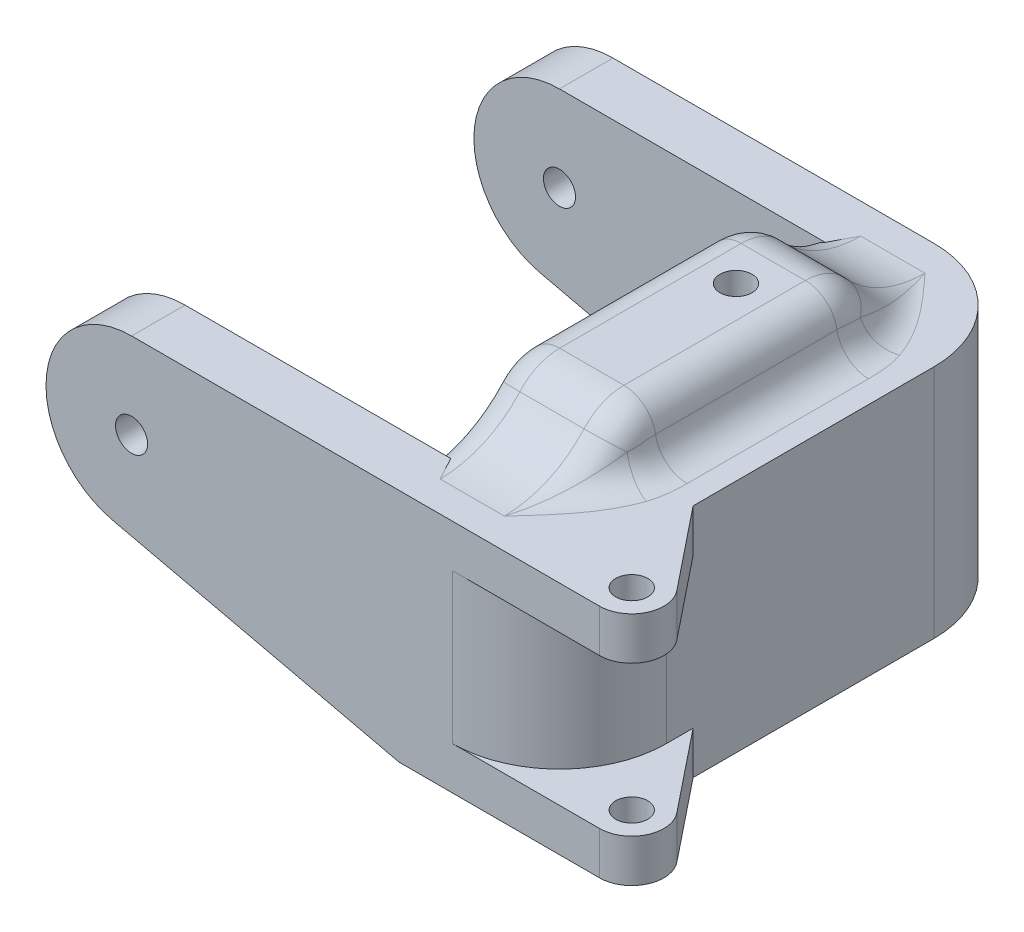
SolidWorks part; units mm, degrees
ref_plane "前视基准面" through (0, 0, 0) normal (0, 0, 1) x (1, 0, 0)
ref_plane "上视基准面" through (0, 0, 0) normal (0, 1, 0) x (1, 0, 0)
ref_plane "右视基准面" through (0, 0, 0) normal (1, 0, 0) x (0, 0, -1)
sketch "草图1" plane through (0, 0, 0) normal (0, 0, 1) x (1, 0, 0)
  line L0 (0.5609, -11) -> (27.3655, -4.7938)
  line L1 (0.5609, -11) -> (-14.4391, -11)
  line L3 (0.5609, 11) -> (-14.4391, 11)
  line L4 (-14.4391, -11) -> (-14.4391, 11)
  line L7 (0.5609, 11) -> (25.5609, 11)
  arc A1 (27.3655, -4.7938) -> (25.5609, 11) centre (25.5609, 3) ccw
  circle A2 centre (25.5609, 3) radius 1.5
  point P0 (0, 0)
  dimension "D4" = 8
  dimension "D5" = 3
  dimension "D1" = 22
  dimension "D2" = 15
  dimension "D3" = 25
extrude "凸台-拉伸1" add sketch "草图1" along normal blind 45
sketch "草图2" plane through (0, 11, 0) normal (0, 1, 0) x (1, 0, 0)
  line L0 (25.5609, 0) -> (-14.4391, 0) construction
  line L1 (-9.4391, -5) -> (42.9728, -5)
  line L2 (-9.4391, -5) -> (-9.4391, -40)
  line L3 (-9.4391, -40) -> (42.9728, -40)
  line L4 (42.9728, -5) -> (42.9728, -40)
  line L7 (-14.4391, -45) -> (-14.4391, 0) construction
  dimension "D1" = 35
  dimension "D2" = 52.4118
  dimension "D3" = 5
  dimension "D4" = 5
extrude "切除-拉伸1" cut sketch "草图2" against normal through all
sketch "草图4" plane through (0, -11, 0) normal (0, -1, 0) x (1, 0, 0)
  line L1 (-9.4391, 40) -> (2.5609, 40)
  line L2 (-9.4391, 40) -> (-9.4391, 33.5)
  line L3 (-9.4391, 33.5) -> (2.5609, 33.5)
  line L4 (2.5609, 40) -> (2.5609, 33.5)
  line L5 (-9.4391, 5) -> (2.5609, 5)
  line L6 (-9.4391, 5) -> (-9.4391, 11.5)
  line L7 (-9.4391, 11.5) -> (2.5609, 11.5)
  line L8 (2.5609, 5) -> (2.5609, 11.5)
  dimension "D1" = 6.5
  dimension "D2" = 12
  dimension "D3" = 6.5
  dimension "D4" = 12
extrude "凸台-拉伸2" add sketch "草图4" against normal blind 12
sketch "草图6" plane through (2.5609, 0, 0) normal (1, 0, 0) x (0, 0, -1)
  line L1 (-33.5, -11) -> (-40, -11)
  line L2 (-33.5, -11) -> (-33.5, -8.5)
  line L3 (-33.5, -8.5) -> (-40, -8.5)
  line L4 (-40, -11) -> (-40, -8.5)
  line L5 (-40, 1) -> (-40, -10.5369) construction
  line L7 (-11.5, -11) -> (-5, -11)
  line L8 (-11.5, -11) -> (-11.5, -8.5)
  line L9 (-11.5, -8.5) -> (-5, -8.5)
  line L10 (-5, -11) -> (-5, -8.5)
  line L11 (-5, -4.7938) -> (-5, -10.5369) construction
  dimension "D1" = 2.5
  dimension "D2" = 6.5
  dimension "D3" = 2.5
  dimension "D4" = 6.5
extrude "切除-拉伸2" cut sketch "草图6" against normal blind 12
sketch "草图7" plane through (0, -8.5, 0) normal (0, -1, 0) x (1, 0, 0)
  line L0 (-1009.4391, 22.5) -> (48990.5609, 22.5) construction
  line L1 (-9.4391, 5) -> (-9.4391, 40) construction
  line L2 (-9.4391, 33.5) -> (2.5609, 33.5) construction
  line L3 (-9.4391, 33.5) -> (-9.4391, 40) construction
  circle A0 centre (-3.4391, 36) radius 1
  circle A1 centre (-3.4391, 9) radius 1
  point P5 (-9.4391, 22.5)
  point P9 (-3.4391, 33.5)
  dimension "D1" = 2.5
  dimension "D2" = 6
extrude "切除-拉伸3" cut sketch "草图7" against normal blind 12
sketch "草图9" plane through (0, -11, 0) normal (0, -1, 0) x (1, 0, 0)
  line L0 (-14.4391, 45) -> (-18.1941, 45)
  line L1 (-20.536, 40.125) -> (-14.4391, 32.51)
  line L3 (-14.4391, 45) -> (-14.4391, 0) construction
  line L4 (-14.4391, 45) -> (-14.4391, 32.51)
  arc A0 (-18.1941, 45) -> (-20.536, 40.125) centre (-18.1941, 42) ccw
  circle A1 centre (-18.1941, 42) radius 1.5
  dimension "D1" = 3
  dimension "D3" = 6
extrude "凸台-拉伸3" add sketch "草图9" against normal blind 22
sketch "草图10" plane through (-14.4391, 0, 0) normal (-1, 0, 0) x (0, 0, 1)
  line L0 (40.125, 0) -> (-49959.875, 0) construction
  line L1 (40.125, 11) -> (40.125, -11) construction
  line L3 (50.1195, -7) -> (30.1305, -7)
  line L4 (50.1195, -7) -> (50.1195, 7)
  line L5 (50.1195, 7) -> (30.1305, 7)
  line L6 (30.1305, -7) -> (30.1305, 7)
  line L7 (50.1195, -7) -> (30.1305, 7) construction
  line L8 (50.1195, 7) -> (30.1305, -7) construction
  point P4 (40.125, 0)
  point P5 (40.125, 0)
  dimension "D1" = 14
  dimension "D2" = 19.9889
extrude "切除-拉伸4" cut sketch "草图10" along normal through all
sketch "草图12" plane through (0, 1, 0) normal (0, 1, 0) x (1, 0, 0)
  line L1 (-9.4391, -5) -> (2.5609, -5)
  line L2 (-9.4391, -5) -> (-9.4391, -11.5)
  line L3 (-9.4391, -11.5) -> (2.5609, -11.5)
  line L4 (2.5609, -5) -> (2.5609, -11.5)
  line L5 (-9.4391, -33.5) -> (2.5609, -33.5)
  line L6 (-9.4391, -33.5) -> (-9.4391, -40)
  line L7 (-9.4391, -40) -> (2.5609, -40)
  line L8 (2.5609, -33.5) -> (2.5609, -40)
  dimension "D1" = 6.5
  dimension "D2" = 12
  dimension "D3" = 6.5
  dimension "D4" = 12
extrude "切除-拉伸5" cut sketch "草图12" against normal blind 6
sketch "草图13" plane through (-9.4391, 0, 0) normal (1, 0, 0) x (0, 0, -1)
  line L1 (-40, 11) -> (-5, 11)
  line L2 (-40, 11) -> (-40, 7)
  line L3 (-40, 7) -> (-5, 7)
  line L4 (-5, 11) -> (-5, 7)
  line L5 (-5, -5) -> (-5, 11) construction
  dimension "D1" = 4
  dimension "D2" = 35
extrude "凸台-拉伸4" add sketch "草图13" along normal blind 12
sketch "草图14" plane through (0, 11, 0) normal (0, 1, 0) x (1, 0, 0)
  line L1 (-9.4391, -33.5) -> (2.5609, -33.5)
  line L2 (-9.4391, -33.5) -> (-9.4391, -11.5)
  line L3 (-9.4391, -11.5) -> (2.5609, -11.5)
  line L4 (2.5609, -33.5) -> (2.5609, -11.5)
  dimension "D1" = 22
  dimension "D2" = 12
extrude "凸台-拉伸5" add sketch "草图14" along normal blind 5
sketch "草图15" plane through (0, 7, 0) normal (0, -1, 0) x (1, 0, 0)
  line L1 (2.5609, 11.5) -> (-9.4391, 11.5)
  line L2 (2.5609, 11.5) -> (2.5609, 33.5)
  line L3 (2.5609, 33.5) -> (-9.4391, 33.5)
  line L4 (-9.4391, 11.5) -> (-9.4391, 33.5)
  dimension "D1" = 22
  dimension "D2" = 12
extrude "切除-拉伸6" cut sketch "草图15" against normal blind 3
fillet "圆角1" radius 10 2 edges at (-3.4391, 11, 11.5) (-3.4391, 11, 33.5)
fillet "圆角2" radius 5 2 edges at (-3.4391, 16, 11.5) (-3.4391, 16, 33.5)
fillet "圆角4" radius 5 2 edges at (-3.4391, 7, 11.5) (-3.4391, 7, 33.5)
sketch "草图16" plane through (0, 10, 0) normal (0, -1, 0) x (1, 0, 0)
  circle A0 centre (-3.4391, 17.5) radius 1.5
  dimension "D1" = 3
extrude "切除-拉伸7" cut sketch "草图16" against normal blind 10
fillet "圆角7" radius 3 5 edges at (-9.4391, 11.8713, 6.9222) (-9.4391, 15.5644, 11.9788) (-9.4391, 16, 22.5) (-9.4391, 15.5644, 33.0212) (-9.4391, 11.8713, 38.0778)
fillet "圆角8" radius 3 3 edges at (-8.9752, 11, 8.308) (-8.9752, 11, 36.692) (-9.4391, 11, 22.5)
sketch "草图17" plane through (0, 10, 0) normal (0, -1, 0) x (1, 0, 0)
  line L1 (-3.4391, 20.0981) -> (-5.6891, 18.799)
  line L2 (-5.6891, 18.799) -> (-5.6891, 16.201)
  line L3 (-5.6891, 16.201) -> (-3.4391, 14.9019)
  line L4 (-3.4391, 14.9019) -> (-1.1891, 16.201)
  line L5 (-1.1891, 16.201) -> (-1.1891, 18.799)
  line L6 (-1.1891, 18.799) -> (-3.4391, 20.0981)
  circle A0 centre (-3.4391, 17.5) radius 2.25 construction
  point P1 (-1.1891, 17.5)
  dimension "D1" = 4.5
extrude "切除-拉伸8" cut sketch "草图17" against normal blind 2
fillet "圆角9" radius 3 5 edges at (2.5609, 15.5644, 33.0212) (2.5609, 15.5644, 11.9788) (2.5609, 11.8713, 6.9222) (2.5609, 11.8713, 38.0778) (2.5609, 16, 22.5)
ref_plane "基准面2" through (-24.4391, 0, 0) normal (-1, 0, 0) x (0, 0, 1)
mirror "镜向2" about plane through (-24.4391, 0, 0) normal (-1, 0, 0) of bodies 118
delete or keep bodies "实体-删除/保留 2" type delete bodies bodies 118
fillet "圆角10" radius 10 2 edges at (-34.4391, 0, 0) (-34.4391, 0, 45)
